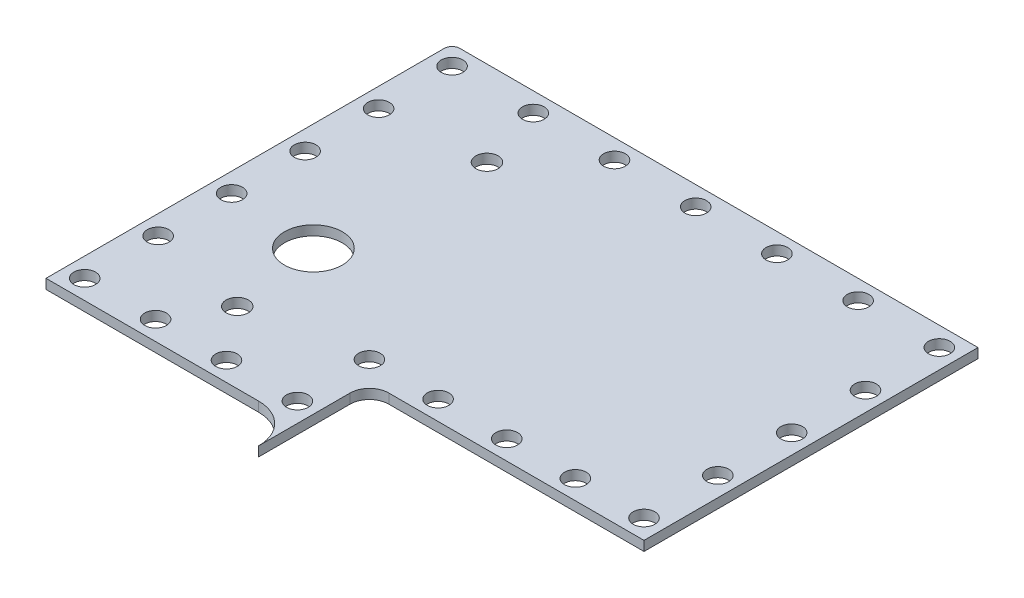
SolidWorks part; units mm, degrees
material "Zoltek Panex 33"
ref_plane "Front Plane" through (0, 0, 0) normal (0, 0, 1) x (1, 0, 0)
ref_plane "Top Plane" through (0, 0, 0) normal (0, 1, 0) x (1, 0, 0)
ref_plane "Right Plane" through (0, 0, 0) normal (1, 0, 0) x (0, 0, -1)
other "Bounding Box"
ref_plane "Default Plane" through (-8.9266, -12.7485, 0) normal (-0.1736, 0.9848, 0) x (0.9848, 0.1736, 0)
sketch "Sketch1" plane through (0, 0, 0) normal (0, 1, 0) x (1, 0, 0)
  line B0 (-8.89, -66.675) -> (-43.815, -66.675)
  line B1 (-43.815, -66.675) -> (-43.815, -1.27)
  line B2 (-42.545, 0) -> (42.545, 0)
  line B3 (42.545, 0) -> (42.545, -54.8431)
  line B4 (42.545, -54.8431) -> (-2.54, -54.8431)
  line B5 (-2.54, -54.8431) -> (-2.54, -73.025)
  arc B6 (-2.54, -73.025) -> (-8.89, -66.675) centre (-8.89, -73.025) ccw
  arc B7 (-42.545, 0) -> (-43.815, -1.27) centre (-42.545, -1.27) ccw
sketch_block_instance "Right Side sketch block-1"
sketch_block "Right Side sketch block"
extrude "Boss-Extrude1" add sketch "Sketch1" along normal blind 1.5875
fillet "Fillet1" radius 3.175 1 edges at (-2.54, 0.7937, 54.8431)
sketch "Sketch2" plane through (0, 1.5875, 0) normal (0, 1, 0) x (-1, 0, 0)
  line L0 (43.815, 1.27) -> (43.815, 66.675) construction
  line L1 (-42.545, 0) -> (42.545, 0) construction
  circle A0 centre (26.115, 40.4703) radius 4.75
  circle A1 centre (24.115, 54.9704) radius 1.83
  circle A2 centre (24.1149, 13.97) radius 1.83
  line B0 (21.0839, 12.2202) -> (17.115, 19.4702)
  line B1 (17.115, 19.4702) -> (17.115, 49.4704)
  line B2 (17.115, 49.4704) -> (21.0839, 56.7204)
  line B3 (31.115, 49.4704) -> (27.1461, 56.7204)
  line B4 (31.115, 49.4704) -> (31.115, 19.4702)
  line B5 (31.115, 19.4702) -> (27.1461, 12.2202)
  circle B6 centre (24.1149, 13.97) radius 1.83
  circle B7 centre (24.115, 54.9704) radius 1.83
  circle B8 centre (26.115, 40.4703) radius 4.75
  arc B9 (21.0839, 12.2202) -> (27.1461, 12.2202) centre (24.115, 13.9702) ccw
  arc B10 (27.1461, 56.7204) -> (21.0839, 56.7204) centre (24.115, 54.9705) ccw
  dimension "D1" = 12.7
  dimension "D2" = 13.97
sketch_block_instance "Switch+PD+Bord+V1-1"
sketch_block "Switch+PD+Bord+V1" parameters "D1"=9.5001, "D2"=3.66, "D3"=3.5
extrude "Cut-Extrude1" cut sketch "Sketch2" against normal through all both and the other way through all contours A0 | A1 | A2 region at (-26.115, 1.5875, 40.4703) region at (-24.115, 1.5875, 54.9704) region at (-24.1149, 1.5875, 13.97)
sketch "Sketch3" plane through (0, 1.5875, 0) normal (0, 1, 0) x (-1, 0, 0)
  line L0 (-39.37, 3.175) -> (-39.37, 51.6681) construction
  line L1 (-39.37, 51.6681) -> (5.715, 51.6681) construction
  line L2 (5.715, 51.6681) -> (5.715, 63.5) construction
  line L3 (5.715, 63.5) -> (40.64, 63.5) construction
  line L4 (40.64, 63.5) -> (40.64, 3.175) construction
  line L5 (40.64, 3.175) -> (-39.37, 3.175) construction
  line L6 (-42.545, 0) -> (42.545, 0) construction
  line L7 (43.815, 1.27) -> (43.815, 66.675) construction
  line L8 (43.815, 66.675) -> (8.89, 66.675) construction
  line L9 (2.54, 73.025) -> (2.54, 58.0181) construction
  line L10 (-0.635, 54.8431) -> (-42.545, 54.8431) construction
  line L11 (-42.545, 54.8431) -> (-42.545, 0) construction
  circle A1 centre (27.305, 3.175) radius 1.778
  circle A2 centre (13.97, 3.175) radius 1.778
  circle A3 centre (0.635, 3.175) radius 1.778
  circle A4 centre (-12.7, 3.175) radius 1.778
  circle A5 centre (-26.035, 3.175) radius 1.778
  circle A6 centre (-39.37, 3.175) radius 1.778
  circle A7 centre (-39.37, 15.2983) radius 1.778
  circle A8 centre (-39.37, 27.4215) radius 1.778
  circle A9 centre (-39.37, 39.5448) radius 1.778
  circle A10 centre (-39.37, 51.6681) radius 1.778
  circle A11 centre (-28.0987, 51.6681) radius 1.778
  circle A12 centre (-16.8275, 51.6681) radius 1.778
  circle A13 centre (-5.5562, 51.6681) radius 1.778
  circle A14 centre (5.715, 51.6681) radius 1.778
  circle A15 centre (5.715, 63.5) radius 1.778
  circle A16 centre (17.3567, 63.5) radius 1.778
  circle A17 centre (28.9983, 63.5) radius 1.778
  circle A18 centre (40.64, 63.5) radius 1.778
  circle A19 centre (40.64, 51.435) radius 1.778
  circle A20 centre (40.64, 39.37) radius 1.778
  circle A21 centre (40.64, 27.305) radius 1.778
  circle A22 centre (40.64, 15.24) radius 1.778
  circle A24 centre (40.64, 3.175) radius 1.778 [skipped]
  circle A25 centre (40.64, 3.175) radius 1.778
  dimension "D7" = 3.556
  dimension "D14" = 13.335
  dimension "D15" = 13.335
  dimension "D18" = 13.335
  dimension "D1" = 3.175
  dimension "D2" = 3.175
  dimension "D3" = 3.175
  dimension "D4" = 3.175
  dimension "D5" = 3.175
  dimension "D6" = 3.175
  dimension "D8" = 12.065
  dimension "D16" = 13.335
  dimension "D17" = 13.335
  dimension "D9" = 5
  dimension "D10" = 5
  dimension "D11" = 2
  dimension "D12" = 4
  dimension "D13" = 6
extrude "Cut-Extrude2" cut sketch "Sketch3" against normal through all both and the other way through all
